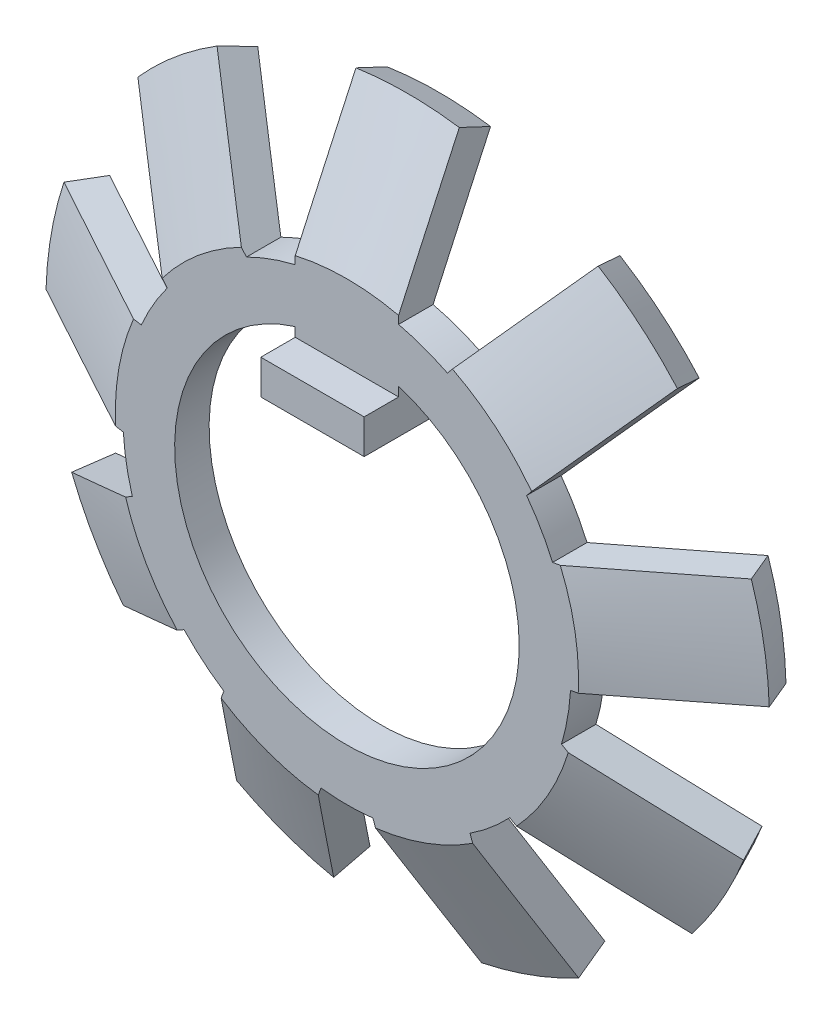
SolidWorks part; units mm, degrees
ref_plane "Front Plane" through (0, 0, 0) normal (0, 0, 1) x (1, 0, 0)
ref_plane "Top Plane" through (0, 0, 0) normal (0, 1, 0) x (1, 0, 0)
ref_plane "Right Plane" through (0, 0, 0) normal (1, 0, 0) x (0, 0, -1)
ref_axis "Axis1" through (0, 0, -1.8016) along (0, 0, 1)
sketch "Sketch1" plane through (0, 0, 0) normal (1, 0, 0) x (0, 0, -1)
  line L0 (0.7619, 10.5) -> (-1, 6.7217)
  line L1 (-1, 6.7217) -> (-1, 5)
  line L2 (-1, 5) -> (0, 5)
  line L3 (0, 5) -> (0, 6.5)
  line L4 (0, 6.5) -> (1.6682, 10.0774)
  line L5 (1.6682, 10.0774) -> (0.7619, 10.5)
  line L6 (0, 0) -> (-1, 0) construction
  dimension "FIX_1" = 25
  dimension "D4." = 13
  dimension "D3." = 21
  dimension "D1_s" = 10
  dimension "T_s" = 1
revolve "Revolve1" add sketch "Sketch1" angle 360 about L6
sketch "Sketch2" plane through (0, 0, 0) normal (0, 0, 1) x (1, 0, 0)
  line L0 (0, 10.5) -> (0, 0) construction
  line L1 (1.5, 10.3923) -> (1.5, 6.3246)
  line L2 (0, 0) -> (3.5912, 9.8668) construction
  line L3 (-1.5, 10.3923) -> (-1.5, 6.3246) construction
  line L4 (2.9163, 5.8091) -> (5.531, 8.9251)
  circle A0 centre (0, 0) radius 6.5 construction
  circle A1 centre (0, 0) radius 10.5 construction
  arc A2 (2.9163, 5.8091) -> (1.5, 6.3246) centre (0, 0) ccw
  arc A3 (5.531, 8.9251) -> (1.5, 10.3923) centre (0, 0) ccw
  dimension "D4." = 13
  dimension "D3." = 21
  dimension "S1" = 3
  dimension "KSS_1" = 40
extrude "Cut-Extrude1" cut sketch "Sketch2" against normal through all and the other way through all
pattern_circular "CirPattern1" count 9 over 360 about axis through (0, 0, -1.8016) along (0, 0, 1) of "Cut-Extrude1"
sketch "Sketch3" plane through (0, 0, 0) normal (1, 0, 0) x (0, 0, -1)
  line L0 (-2, 0) -> (0, 0) construction
  line L1 (-2, 4.5) -> (-1, 4.5)
  line L2 (-2, 4.5) -> (-2, 3.5)
  line L3 (-2, 3.5) -> (0, 3.5)
  line L4 (0, 5) -> (0, 3.5)
  line L5 (-1, 4.5) -> (-1, 5)
  line L6 (-1, 5) -> (0, 5)
  line L7 (0, -5) -> (-2, -5) construction
  dimension "V" = 2
  dimension "K_s" = 8.5
  dimension "D1_s" = 10
  dimension "T_s" = 1
extrude "Boss-Extrude1" add sketch "Sketch3" along normal mid plane 3
equation "\"KSS_1@Sketch2\" = 360 / \"Teeth\""
equation "\"KSS_2@CirPattern1\" = 360 / \"Teeth\""
